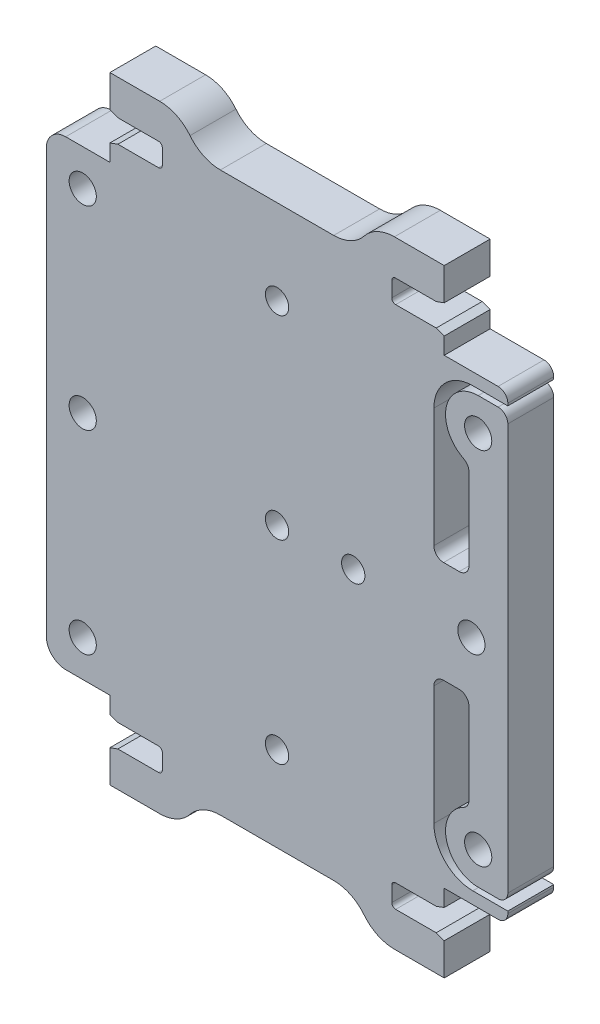
SolidWorks part; units mm, degrees
ref_plane "Front Plane" through (0, 0, 0) normal (0, 0, 1) x (1, 0, 0)
ref_plane "Top Plane" through (0, 0, 0) normal (0, 1, 0) x (1, 0, 0)
ref_plane "Right Plane" through (0, 0, 0) normal (1, 0, 0) x (0, 0, -1)
sketch "Sketch1" plane through (0, 0, 0) normal (0, 0, 1) x (1, 0, 0)
  line L0 (26.289, 30.1625) -> (26.289, -30.1625) construction
  line L1 (-30.1625, -30.1625) -> (30.1625, -30.1625)
  line L2 (-30.1625, -30.1625) -> (-30.1625, 30.1625)
  line L3 (-30.1625, 30.1625) -> (30.1625, 30.1625)
  line L4 (30.1625, -30.1625) -> (30.1625, 30.1625)
  line L5 (-30.1625, -30.1625) -> (30.1625, 30.1625) construction
  line L6 (-30.1625, 30.1625) -> (30.1625, -30.1625) construction
  line L7 (-25.4, -25.4) -> (25.4, -25.4) construction
  line L8 (-25.4, -25.4) -> (-25.4, 25.4) construction
  line L9 (-25.4, 25.4) -> (25.4, 25.4) construction
  line L10 (25.4, -25.4) -> (25.4, 25.4) construction
  line L11 (-25.4, -25.4) -> (25.4, 25.4) construction
  line L12 (-25.4, 25.4) -> (25.4, -25.4) construction
  line L13 (0, 0) -> (30.1625, 0) construction
  circle A0 centre (-25.4, 25.4) radius 11 construction
  circle A1 centre (26.289, 23.5585) radius 1.778
  circle A2 centre (26.289, 23.5585) radius 11 construction
  circle A3 centre (26.289, -23.5585) radius 1.778
  circle A4 centre (-25.4, 25.4) radius 1.778
  circle A5 centre (-25.4, -25.4) radius 1.778
  circle A6 centre (0, 25.4) radius 1.524
  circle A7 centre (0, 0) radius 1.524
  circle A8 centre (0, -25.4) radius 1.524
  circle A9 centre (-25.4, 0) radius 1.778
  circle A10 centre (9.9593, 0) radius 1.524
  circle A13 centre (25.4, 0) radius 1.778
  point P0 (0, 0)
  point P6 (0, 0)
  point P58 (-14.4, 25.4)
  dimension "D4" = 22
  dimension "D6" = 3.556
  dimension "D15" = 3.048
  dimension "D7" = 6.604
  dimension "D8" = 9.9593
  dimension "D1" = 60.325
  dimension "D2" = 60.325
  dimension "D3" = 4.7625
  dimension "D5" = 0.889
extrude "Boss-Extrude1" add sketch "Sketch1" along normal blind 6
sketch "Sketch5" plane through (0, 0, 6) normal (0, 0, 1) x (1, 0, 0)
  line L0 (20.4978, 23.5585) -> (20.4978, 6.6675)
  line L1 (20.4978, 6.6675) -> (25.0825, 6.6675)
  line L2 (25.0825, 6.6675) -> (25.0825, 19.4654)
  line L3 (26.289, 27.8257) -> (30.1625, 27.8257)
  line L4 (30.1625, -30.1625) -> (30.1625, 30.1625) construction
  line L6 (30.1625, 28.5877) -> (23.4176, 28.5877)
  line L8 (30.1625, 28.5877) -> (30.1625, 27.8257)
  arc A0 (26.289, 27.8257) -> (25.0825, 19.4654) centre (26.289, 23.5585) ccw
  circle A1 centre (26.289, 23.5585) radius 1.778 construction
  arc A3 (20.4978, 23.5585) -> (23.4176, 28.5877) centre (26.289, 23.5585) cw
  dimension "D2" = 1.524
  dimension "D3" = 4.2672
  dimension "D1" = 5.08
  dimension "D4" = 16.891
  dimension "D5" = 0.762
extrude "Cut-Extrude1" cut sketch "Sketch5" against normal through all
fillet "Fillet7" radius 1.27 5 edges at (25.0825, 19.4654, 3) (25.0825, 6.6675, 3) (20.4978, 6.6675, 3) (30.1625, 27.8257, 3) (30.1625, 30.1625, 3)
mirror "Mirror1" about plane through (0, 0, 0) normal (0, 1, 0) of "Cut-Extrude1"
fillet "Fillet8" radius 1.27 5 edges at (25.0825, -19.4654, 3) (25.0825, -6.6675, 3) (20.4978, -6.6675, 3) (30.1625, -27.8257, 3) (30.1625, -30.1625, 3)
fillet "Fillet9" radius 2.54 2 edges at (-30.1625, -30.1625, 3) (-30.1625, 30.1625, 3)
fillet "Fillet15" radius 5.08 2 edges at (23.4176, -28.5877, 3) (23.4176, 28.5877, 3)
sketch "Sketch4" plane through (0, 0, 6) normal (0, 0, 1) x (1, 0, 0)
  line L0 (-27.6225, -30.1625) -> (28.8925, -30.1625) construction
  line L1 (21.8516, 31.75) -> (19.3116, 31.75)
  line L2 (21.8516, 31.75) -> (21.8516, 30.1625)
  line L3 (21.8516, 30.1625) -> (19.3116, 30.1625)
  line L4 (19.3116, 31.75) -> (19.3116, 30.1625)
  line L6 (21.8516, -31.75) -> (19.3116, -31.75)
  line L7 (28.8925, 30.1625) -> (-27.6225, 30.1625) construction
  line L8 (21.8516, -31.75) -> (21.8516, -30.1625)
  line L9 (21.8516, -30.1625) -> (19.3116, -30.1625)
  line L10 (19.3116, -31.75) -> (19.3116, -30.1625)
  line L11 (21.8516, 30.1625) -> (21.8516, 25.4) construction
  line L12 (-21.8516, 30.1625) -> (-19.3116, 30.1625)
  line L13 (-21.8516, 30.1625) -> (-21.8516, 31.75)
  line L14 (-21.8516, 31.75) -> (-19.3116, 31.75)
  line L15 (-19.3116, 30.1625) -> (-19.3116, 31.75)
  line L18 (-21.8516, -30.1625) -> (-19.3116, -30.1625)
  line L19 (-21.8516, -30.1625) -> (-21.8516, -31.75)
  line L20 (-21.8516, -31.75) -> (-19.3116, -31.75)
  line L21 (-19.3116, -30.1625) -> (-19.3116, -31.75)
  line L22 (0, 25.4) -> (-21.8516, 25.4) construction
  line L23 (-21.8516, 25.4) -> (-21.8516, 30.1625) construction
  line L25 (21.8516, 25.4) -> (0, 25.4) construction
  point P0 (0, 0)
  dimension "D1" = 2.54
  dimension "D2" = 1.5875
  dimension "D3" = 43.7032
extrude "Boss-Extrude2" add sketch "Sketch4" against normal up to surface (6 mm away) up to face at (27.178, 0, 0)
sketch "Sketch6" plane through (0, 0, 6) normal (0, 0, 1) x (1, 0, 0)
  line L0 (19.3116, 30.1625) -> (-19.3116, 30.1625) construction
  line L1 (-6.35, 30.1625) -> (6.35, 30.1625)
  line L2 (-6.35, 30.1625) -> (-6.35, 36.5125)
  line L3 (-6.35, 36.5125) -> (6.35, 36.5125)
  line L4 (6.35, 30.1625) -> (6.35, 36.5125)
  line L5 (0, 30.1625) -> (0, 0) construction
  dimension "D1" = 12.7
  dimension "D2" = 6.35
extrude "Boss-Extrude3" add sketch "Sketch6" against normal up to surface (6 mm away) up to face at (27.178, 0, 0)
fillet "Fillet10" radius 2.54 4 edges at (6.35, 30.1625, 3) (6.35, 36.5125, 3) (-6.35, 30.1625, 3) (-6.35, 36.5125, 3)
mirror "Mirror2" about plane through (0, 0, 0) normal (0, 1, 0) of "Boss-Extrude3"
fillet "Fillet11" radius 2.54 4 edges at (6.35, -30.1625, 3) (6.35, -36.5125, 3) (-6.35, -36.5125, 3) (-6.35, -30.1625, 3)
sketch "Sketch7" plane through (0, 0, 6) normal (0, 0, 1) x (1, 0, 0)
  line L0 (3.81, 36.5125) -> (-3.81, 36.5125) construction
  line L1 (-21.8516, 30.1625) -> (21.8516, 30.1625)
  line L2 (-21.8516, 30.1625) -> (-21.8516, 36.5125)
  line L3 (-21.8516, 36.5125) -> (21.8516, 36.5125) construction
  line L4 (21.8516, 30.1625) -> (21.8516, 36.5125)
  line L5 (3.81, -36.5125) -> (-3.81, -36.5125) construction
  line L6 (-21.8516, -30.1625) -> (21.8516, -30.1625)
  line L7 (-21.8516, -30.1625) -> (-21.8516, -36.5125)
  line L8 (-21.8516, -36.5125) -> (21.8516, -36.5125) construction
  line L9 (21.8516, -30.1625) -> (21.8516, -36.5125)
  line L10 (-10.4216, 36.5125) -> (10.4216, 36.5125)
  line L11 (-21.8516, 36.5125) -> (-10.4216, 36.5125) construction
  line L12 (-21.8516, 36.5125) -> (-21.8516, 40.3225)
  line L13 (-21.8516, 40.3225) -> (-10.4216, 40.3225)
  line L14 (-10.4216, 36.5125) -> (-10.4216, 40.3225)
  line L15 (21.8516, 36.5125) -> (10.4216, 36.5125) construction
  line L16 (21.8516, 36.5125) -> (21.8516, 40.3225)
  line L17 (21.8516, 40.3225) -> (10.4216, 40.3225)
  line L18 (10.4216, 36.5125) -> (10.4216, 40.3225)
  line L19 (-21.8516, -36.5125) -> (-10.4216, -36.5125) construction
  line L20 (-21.8516, -36.5125) -> (-21.8516, -40.3225)
  line L21 (-21.8516, -40.3225) -> (-10.4216, -40.3225)
  line L22 (-10.4216, -36.5125) -> (-10.4216, -40.3225)
  line L23 (21.8516, -36.5125) -> (10.4216, -36.5125) construction
  line L24 (21.8516, -36.5125) -> (21.8516, -40.3225)
  line L25 (21.8516, -40.3225) -> (10.4216, -40.3225)
  line L26 (10.4216, -36.5125) -> (10.4216, -40.3225)
  line L27 (-10.4216, -36.5125) -> (10.4216, -36.5125)
  dimension "D1" = 10.16
  dimension "D2" = 11.43
extrude "Boss-Extrude4" add sketch "Sketch7" against normal up to surface (6 mm away) up to face at (27.178, 0, 0)
fillet "Fillet12" radius 5.08 4 edges at (-10.4216, -40.3225, 3) (10.4216, -40.3225, 3) (10.4216, 40.3225, 3) (-10.4216, 40.3225, 3)
fillet "Fillet13" radius 5.08 4 edges at (-10.4216, -36.5125, 3) (10.4216, -36.5125, 3) (-10.4216, 36.5125, 3) (10.4216, 36.5125, 3)
sketch "Sketch9" plane through (0, 0, 0) normal (0, 0, -1) x (-1, 0, 0)
  line L0 (-21.8516, 30.1625) -> (-21.8516, 40.3225) construction
  line L1 (-21.8516, 35.7251) -> (-14.9936, 35.7251)
  line L2 (-21.8516, 35.7251) -> (-21.8516, 32.7279)
  line L3 (-21.8516, 32.7279) -> (-14.9936, 32.7279)
  line L4 (-14.9936, 35.7251) -> (-14.9936, 32.7279)
  line L5 (21.8516, 40.3225) -> (21.8516, 30.1625) construction
  line L6 (21.8516, 35.7251) -> (14.9936, 35.7251)
  line L7 (21.8516, 35.7251) -> (21.8516, 32.7279)
  line L8 (21.8516, 32.7279) -> (14.9936, 32.7279)
  line L9 (14.9936, 35.7251) -> (14.9936, 32.7279)
  line L10 (-21.8516, -40.3225) -> (-21.8516, -30.1625) construction
  line L11 (-21.8516, -32.7279) -> (-14.9936, -32.7279)
  line L12 (-21.8516, -32.7279) -> (-21.8516, -35.7251)
  line L13 (-21.8516, -35.7251) -> (-14.9936, -35.7251)
  line L14 (-14.9936, -32.7279) -> (-14.9936, -35.7251)
  line L15 (21.8516, -30.1625) -> (21.8516, -40.3225) construction
  line L16 (21.8516, -32.7279) -> (14.9936, -32.7279)
  line L17 (21.8516, -32.7279) -> (21.8516, -35.7251)
  line L18 (21.8516, -35.7251) -> (14.9936, -35.7251)
  line L19 (14.9936, -32.7279) -> (14.9936, -35.7251)
  line L20 (-14.9936, 34.2265) -> (-21.8516, 34.2265) construction
  line L21 (-14.9936, -34.2265) -> (-21.8516, -34.2265) construction
  line L22 (-21.8516, -30.1625) -> (-28.8925, -30.1625) construction
  line L23 (-28.8925, 30.1625) -> (-21.8516, 30.1625) construction
  dimension "D1" = 6.858
  dimension "D2" = 2.9972
  dimension "D3" = 4.064
  dimension "D4" = 4.064
extrude "Cut-Extrude2" cut sketch "Sketch9" against normal up to next
chamfer "Chamfer1" distance 0.381 angle 70 8 edges at (21.8516, 32.7279, 3) (21.8516, 35.7251, 3) (-21.8516, 35.7251, 3) (-21.8516, 32.7279, 3) (21.8516, -35.7251, 3) (21.8516, -32.7279, 3) (-21.8516, -32.7279, 3) (-21.8516, -35.7251, 3)
fillet "Fillet14" radius 0.508 8 edges at (14.9936, 35.7251, 3) (14.9936, -32.7279, 3) (-14.9936, 35.7251, 3) (-14.9936, -32.7279, 3) (-14.9936, 32.7279, 3) (-14.9936, -35.7251, 3) (14.9936, -35.7251, 3) (14.9936, 32.7279, 3)
